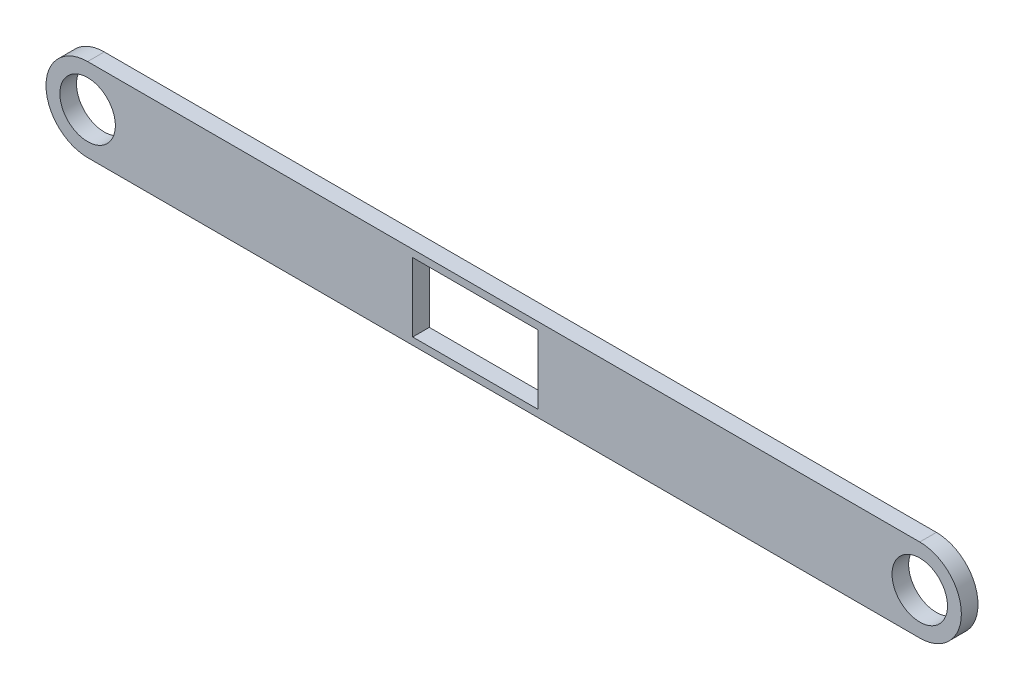
SolidWorks part; units mm, degrees
material "Acrylic (Medium-high impact)"
ref_plane "Front Plane" through (0, 0, 0) normal (0, 0, 1) x (1, 0, 0)
ref_plane "Top Plane" through (0, 0, 0) normal (0, 1, 0) x (1, 0, 0)
ref_plane "Right Plane" through (0, 0, 0) normal (1, 0, 0) x (0, 0, -1)
sketch "Sketch1" plane through (0, 0, 0) normal (0, 0, 1) x (1, 0, 0)
  line L0 (75, 0) -> (-75, 0) construction
  line L1 (75, -7.5) -> (-75, -7.5)
  line L2 (75, 7.5) -> (-75, 7.5)
  line L3 (0, 7.5) -> (0, -7.5) construction
  line L5 (-16.4, 6.2) -> (6.2, 6.2)
  line L6 (-16.4, 6.2) -> (-16.4, -6.2)
  line L7 (-16.4, -6.2) -> (6.2, -6.2)
  line L8 (6.2, 6.2) -> (6.2, -6.2)
  line L9 (-16.4, 6.2) -> (6.2, -6.2) construction
  line L10 (-16.4, -6.2) -> (6.2, 6.2) construction
  arc A0 (75, -7.5) -> (75, 7.5) centre (75, 0) ccw
  arc A1 (-75, 7.5) -> (-75, -7.5) centre (-75, 0) ccw
  circle A2 centre (75, 0) radius 5
  circle A3 centre (-75, 0) radius 5
  point P2 (0, 0)
  point P14 (-5.1, 0)
  point P21 (0, 0)
  dimension "D2" = 10
  dimension "D1" = 150
  dimension "D3" = 15
  dimension "D4" = 22.6
  dimension "D5" = 12.4
  dimension "D6" = 6.2
extrude "Boss-Extrude1" add sketch "Sketch1" along normal blind 3
